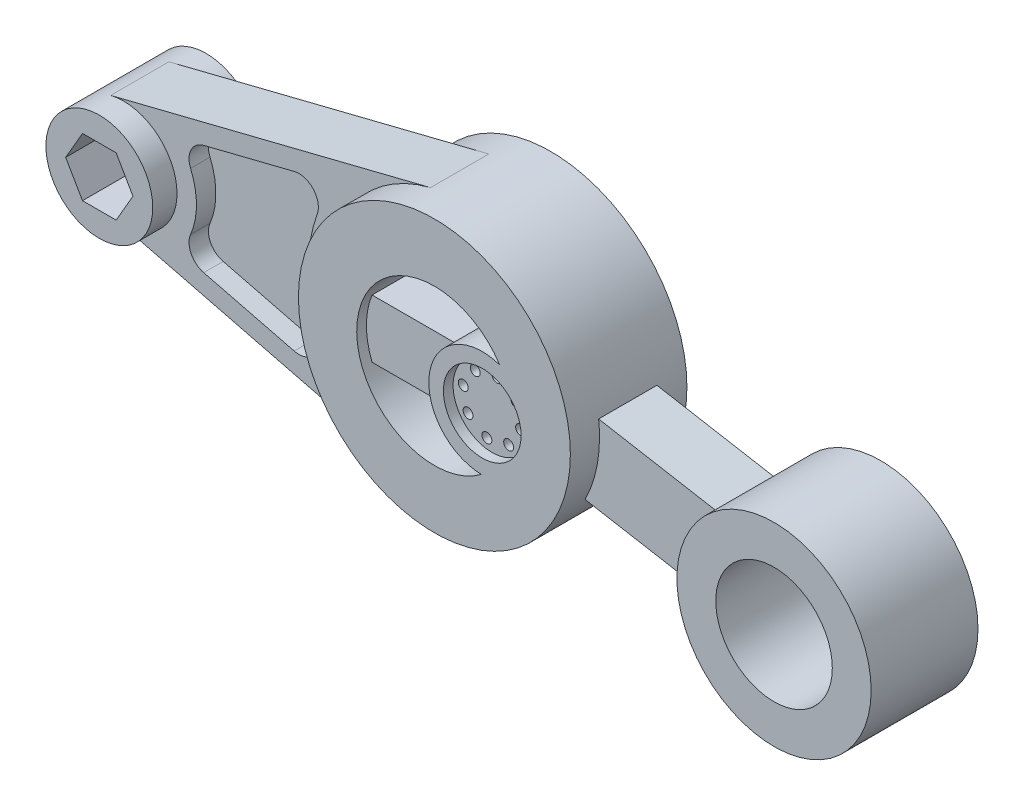
SolidWorks part; units mm, degrees
material "Copper"
ref_plane "Front Plane" through (0, 0, 0) normal (0, 0, 1) x (1, 0, 0)
ref_plane "Top Plane" through (0, 0, 0) normal (0, 1, 0) x (1, 0, 0)
ref_plane "Right Plane" through (0, 0, 0) normal (1, 0, 0) x (0, 0, -1)
ref_plane "CENTRE_Plane" through (175, 0, 0) normal (1, 0, 0) x (0, 0, -1)
ref_axis "CENTRE_Plane_Axis" through (175, 0, 33) along (0, 0, -1)
ref_plane "CENTRE_RIGHT_Plane" through (169.7231, -29.9268, 0) normal (0.9848, -0.1736, 0) x (0, 0, -1)
ref_plane "RIGHT_Plane" through (342.0645, -60.3152, 0) normal (0.9848, -0.1736, 0) x (0, 0, -1)
sketch "Sketch1" plane through (0, 0, 0) normal (0, 0, 1) x (1, 0, 0)
  line L0 (-6.6786, 26.6767) -> (158, 67.9043)
  line L1 (-6.6786, -26.6767) -> (158, -67.9043)
  arc A0 (-6.6786, 26.6767) -> (-6.6786, -26.6767) centre (0, 0) ccw
  arc A1 (158, -67.9043) -> (158, 67.9043) centre (175, 0) ccw
  dimension "D1" = 55
  dimension "D2" = 140
extrude "LEFT_ARM" add sketch "Sketch1" along normal mid plane 30
sketch "Sketch2" plane through (0, 0, 0) normal (0, 0, 1) x (1, 0, 0)
  circle A0 centre (0, 0) radius 27.5
  dimension "D1" = 55
extrude "LEFT_Boss" add sketch "Sketch2" along normal mid plane 55
sketch "Sketch4" plane through (0, 0, 27.5) normal (0, 0, 1) x (1, 0, 0)
  line L0 (33, 0) -> (-33, 0) construction
  line L1 (17.3205, 0) -> (8.6603, 15)
  line L2 (8.6603, 15) -> (-8.6603, 15)
  line L3 (-8.6603, 15) -> (-17.3205, 0)
  line L4 (-17.3205, 0) -> (-8.6603, -15)
  line L5 (-8.6603, -15) -> (8.6603, -15)
  line L6 (8.6603, -15) -> (17.3205, 0)
  circle A0 centre (0, 0) radius 15 construction
  dimension "D1" = 30
extrude "LEFT_Hex" cut sketch "Sketch4" against normal through all both and the other way through all
sketch "Sketch3" plane through (0, 0, 0) normal (0, 0, 1) x (1, 0, 0)
  circle A0 centre (175, 0) radius 70
  dimension "D1" = 140
extrude "CENTRE_Boss" add sketch "Sketch3" along normal mid plane 60
sketch "Sketch5" plane through (169.7231, -29.9268, 0) normal (0.9848, -0.1736, 0) x (0, 0, -1)
  line L0 (-33, 30.3884) -> (33, 30.3884) construction
  line L1 (-15, 10.3884) -> (15, 10.3884)
  line L2 (-15, 10.3884) -> (-15, 50.3884)
  line L3 (-15, 50.3884) -> (15, 50.3884)
  line L4 (15, 10.3884) -> (15, 50.3884)
  line L5 (-15, 10.3884) -> (15, 50.3884) construction
  line L6 (-15, 50.3884) -> (15, 10.3884) construction
  line L7 (0, 90.9113) -> (0, -90.9113) construction
  point P0 (0, 30.3884)
  dimension "D1" = 30
  dimension "D2" = 40
extrude "RIGHT_ARM" add sketch "Sketch5" along normal up to surface (175 mm away) up to plane "RIGHT_Plane"
sketch "RIGHT_ARM_CL" plane through (0, 0, 0) normal (0, 0, 1) x (1, 0, 0)
  line L0 (175, 0) -> (347.3414, -30.3884) construction
  line L1 (331.795, -118.556) -> (352.3339, -2.0744) construction
sketch "Sketch7" plane through (0, 0, 0) normal (0, 0, 1) x (1, 0, 0)
  circle A0 centre (347.3414, -30.3884) radius 50
  dimension "D1" = 100
extrude "RIGHT_Boss" add sketch "Sketch7" along normal mid plane 55
sketch "Sketch8" plane through (0, 0, 27.5) normal (0, 0, 1) x (1, 0, 0)
  circle A0 centre (347.3414, -30.3884) radius 30
  dimension "D1" = 60
extrude "RIGHT_Boss_Hole" cut sketch "Sketch8" against normal through all
sketch "Sketch9" plane through (0, 0, 30) normal (0, 0, 1) x (1, 0, 0)
  circle A0 centre (175, 0) radius 40
  dimension "D1" = 80
extrude "CENTRE_Hole" cut sketch "Sketch9" against normal through all
sketch "Sketch10" plane through (0, 0, 0) normal (0, 0, 1) x (1, 0, 0)
  line L0 (175, 0) -> (347.3414, -30.3884) construction
  line L1 (159.2174, -89.5076) -> (180.2288, 29.6541) construction
  circle A0 centre (199.6202, -4.3412) radius 27.5
  dimension "D1" = 55
  dimension "D2" = 25
extrude "CENTRE_Blob" add sketch "Sketch10" along normal mid plane 60
sketch "Sketch11" plane through (175, 0, 0) normal (1, 0, 0) x (0, 0, -1)
  line L1 (-25, -15) -> (25, -15)
  line L2 (-25, -15) -> (-25, 15)
  line L3 (-25, 15) -> (25, 15)
  line L4 (25, -15) -> (25, 15)
  line L5 (-25, -15) -> (25, 15) construction
  line L6 (-25, 15) -> (25, -15) construction
  point P0 (0, 0)
  dimension "D1" = 50
  dimension "D2" = 30
extrude "CENTRE_Beam" add sketch "Sketch11" along normal up to next and the other way up to next
sketch "Sketch12" plane through (0, 0, 30) normal (0, 0, 1) x (1, 0, 0)
  circle A0 centre (199.6202, -4.3412) radius 20
  dimension "D1" = 40
extrude "Cut-Extrude4" cut sketch "Sketch12" against normal blind 5
hole_wizard "1/4-20 Tapped Hole1" positions "Sketch13" profile "Sketch14" tap size "1/4-20" standard "ANSI Inch" end condition up to next
sketch "Sketch13" plane through (0, 0, 25) normal (0, 0, 1) x (1, 0, 0)
  line L0 (175, 0) -> (347.3414, -30.3884) construction
  circle A0 centre (199.6202, -4.3412) radius 20 construction
  point P0 (184.8481, -1.7365)
  dimension "D1" = 15
sketch "Sketch14" plane through (184.8481, -1.7365, 25) normal (1, 0, 0) x (0, -1, 0)
  line L0 (0, 0) -> (0, 55)
  line L1 (0, 55) -> (2.5527, 55)
  line L2 (2.5527, 55) -> (2.5527, 0)
  line L5 (2.5527, 0) -> (0, 0)
  line L11 (0, -6.35) -> (0, 107.95) construction
  dimension "Thru Tap Drill Dia." = 5.1054
  dimension "Thru Tap Drill Depth" = 55
cosmetic thread "Hole Thread1" parameters "D2"=6.35
pattern_circular "CirPattern1" count 8 over 360 about axis through (199.6202, -4.3412, 25) along (0, 0, 1) of "1/4-20 Tapped Hole1"
cosmetic thread "Hole Thread2" parameters "D2"=6.35
cosmetic thread "Hole Thread3" parameters "D2"=6.35
cosmetic thread "Hole Thread4" parameters "D2"=6.35
cosmetic thread "Hole Thread5" parameters "D2"=6.35
cosmetic thread "Hole Thread6" parameters "D2"=6.35
cosmetic thread "Hole Thread7" parameters "D2"=6.35
cosmetic thread "Hole Thread8" parameters "D2"=6.35
mirror "Mirror1" about plane through (0, 0, 0) normal (0, 0, 1) of "Cut-Extrude4"
sketch "Sketch15" plane through (0, 0, 15) normal (0, 0, 1) x (1, 0, 0)
  line L24 (109.0977, 45.3529) -> (-4.25, 16.9761)
  line L25 (-4.25, -16.9761) -> (109.0977, -45.3529)
  line L26 (109.0977, 45.3529) -> (27.9233, 25.0307)
  line L27 (27.9233, -25.0307) -> (109.0977, -45.3529)
  arc A12 (109.0977, 45.3529) -> (109.0977, -45.3529) centre (175, 0) ccw
  arc A13 (109.0977, 45.3529) -> (109.0977, -45.3529) centre (175, 0) ccw
  arc A23 (-9.1071, -36.3773) -> (-9.1071, 36.3773) centre (0, 0) ccw
  arc A24 (27.9233, -25.0307) -> (27.9233, 25.0307) centre (0, 0) ccw
  dimension "D1" = 10
  dimension "D2" = 10
extrude "Cut_OUT" cut sketch "Sketch15" against normal blind 10
fillet "Fillet1" radius 10 4 edges at (109.0977, 45.3529, 10) (109.0977, -45.3529, 10) (27.9233, -25.0307, 10) (27.9233, 25.0307, 10)
mirror "Mirror2" about plane through (0, 0, 0) normal (0, 0, 1) of "Fillet1", "Cut_OUT"
sketch "Sketch16" plane through (0, 0, 0) normal (0, 0, 1) x (1, 0, 0)
  line L0 (346.1258, -37.2821) -> (348.5569, -23.4948)
  line L1 (331.795, -118.556) -> (352.3339, -2.0744) construction
  line L2 (348.5569, -23.4948) -> (320.1944, -18.4937)
  line L3 (320.1944, -18.4937) -> (317.7634, -32.281)
  line L4 (317.7634, -32.281) -> (346.1258, -37.2821)
  circle A0 centre (347.3414, -30.3884) radius 30 construction
  point P4 (347.3414, -30.3884)
  dimension "D2" = 28.8
extrude "KEYWAY" [suppressed] cut sketch "Sketch16" against normal through all both and the other way through all
mirror "Mirror3" [suppressed] about plane through (342.0645, -60.3152, 0) normal (0.9848, -0.1736, 0)
equation "\"D1@Sketch2\"=\"D1@Sketch1\""
equation "\"D1@Sketch3\"=\"D2@Sketch1\""
equation "\"D2@Sketch16\"=25+3.8"
